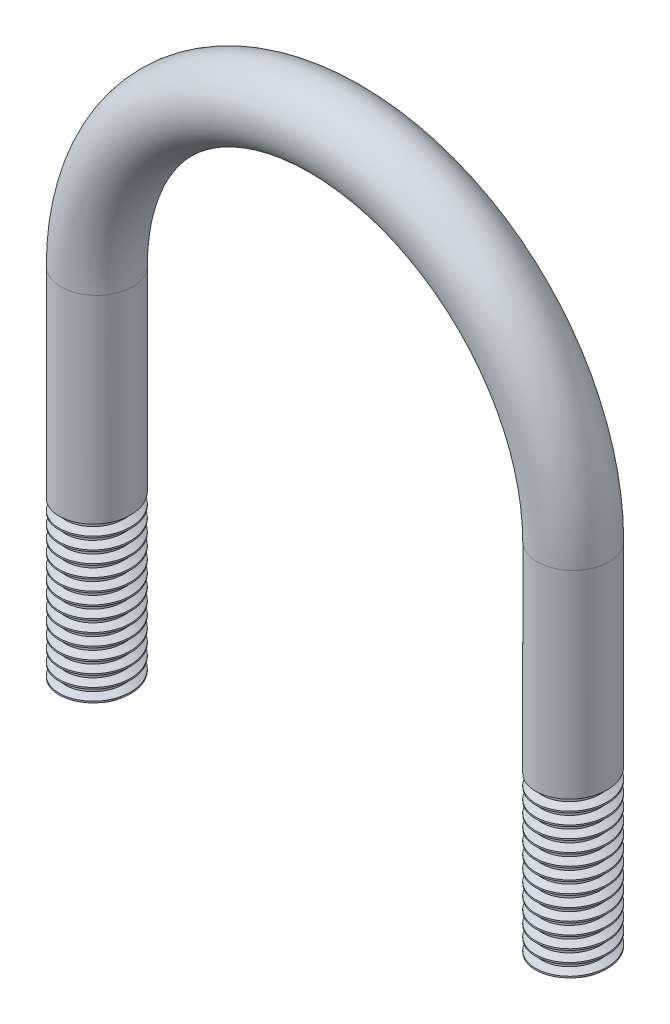
SolidWorks part; units mm, degrees
material "Plain Carbon Steel"
ref_plane "Front Plane" through (0, 0, 0) normal (0, 0, 1) x (1, 0, 0)
ref_plane "Top Plane" through (0, 0, 0) normal (0, 1, 0) x (1, 0, 0)
ref_plane "Right Plane" through (0, 0, 0) normal (1, 0, 0) x (0, 0, -1)
sketch "Sketch1" plane through (0, 0, 0) normal (0, 0, 1) x (1, 0, 0)
  line L0 (-10, 0) -> (10, 0) construction
  line L1 (-8.4, 0) -> (-11.6, 0) construction
  line L2 (0, 0) -> (0, 15) construction
  line L3 (8.4, 0) -> (11.6, 0) construction
  line L4 (-10, 0) -> (-10, 15)
  line L5 (10, 0) -> (10, 15)
  line L6 (8.4, 0) -> (8.4, 15) construction
  line L7 (-8.4, 0) -> (-8.4, 15) construction
  line L8 (11.6, 0) -> (11.6, 15) construction
  line L9 (-11.6, 0) -> (-11.6, 15) construction
  line L10 (0, 23.4) -> (-14.8489, 23.4) construction
  arc A0 (10, 15) -> (-10, 15) centre (0, 15) ccw
  arc A1 (8.4, 15) -> (-8.4, 15) centre (0, 15) ccw construction
  arc A2 (11.6, 15) -> (-11.6, 15) centre (0, 15) ccw construction
  point P3 (0, 0)
  point P6 (-10, 0)
  dimension "D4" = 1.6
  dimension "D1" = 20
  dimension "D2" = 3.2
  dimension "D3" = 15
  dimension "D5" = 1.6
sketch "Sketch2" plane through (0, 0, 0) normal (0, 1, 0) x (1, 0, 0)
  circle A1 centre (-10, 0) radius 1.5
  dimension "D1" = 3
sweep "Sweep1" add profiles "Sketch2" path "Sketch1"
sketch "Sketch3" plane through (0, 0, 0) normal (0, 0, 1) x (1, 0, 0)
  line L2 (0, 23.5) -> (-15.4787, 23.5) construction
  arc A0 (10, 15) -> (-10, 15) centre (0, 15) ccw construction
  arc A1 (10, 15) -> (-10, 15) centre (0, 15) ccw construction
  arc A2 (11.6, 15) -> (-11.6, 15) centre (0, 15) ccw construction
  arc A3 (8.5, 15) -> (-8.5, 15) centre (0, 15) ccw construction
  dimension "D1" = 1.6
  dimension "D2" = 1.5
ref_plane "Plane1" through (0, 23.5, 0) normal (0, 1, 0) x (1, 0, 0)
thread "Thread3" pitch 0.5 method cut profile "Thread Profile3" start angle 0, offset 8, length 0, pitch 0.5, diameter 3
ref_plane "Plane4" through (-11.5, 7, 0) normal (0, 0, 1) x (-1, 0, 0)
sketch "Thread Profile3" plane through (-11.5, 7, 0) normal (0, 0, 1) x (-1, 0, 0)
  line L0 (0, 0) -> (0, 0.5) construction
  line L11 (0, 0) -> (0, 0.4375)
  line L12 (0, 0.4375) -> (-0.2706, 0.2812)
  line L13 (-0.2706, 0.2812) -> (-0.2706, 0.1562)
  line L15 (-0.2706, 0.1562) -> (0, 0)
  line L17 (-0.2706, 0.2187) -> (0, 0.2187) construction
  point P2 (0, 0)
  dimension "Pitch" = 0.5
  dimension "Profile_Angle" = 60
  dimension "Profile_Land" = 0.125
  dimension "Profile_Height" = 0.2706
thread "Thread4" pitch 0.5 method cut profile "Thread Profile4" start angle 0, offset 8, length 0, pitch 0.5, diameter 3
ref_plane "Plane5" through (8.5, 7, 0) normal (0, 0, 1) x (-1, 0, 0)
sketch "Thread Profile4" plane through (8.5, 7, 0) normal (0, 0, 1) x (-1, 0, 0)
  line L0 (0, 0) -> (0, 0.5) construction
  line L11 (0, 0) -> (0, 0.4375)
  line L12 (0, 0.4375) -> (-0.2706, 0.2812)
  line L13 (-0.2706, 0.2812) -> (-0.2706, 0.1562)
  line L15 (-0.2706, 0.1562) -> (0, 0)
  line L17 (-0.2706, 0.2187) -> (0, 0.2187) construction
  point P2 (0, 0)
  dimension "Pitch" = 0.5
  dimension "Profile_Angle" = 60
  dimension "Profile_Land" = 0.125
  dimension "Profile_Height" = 0.2706
